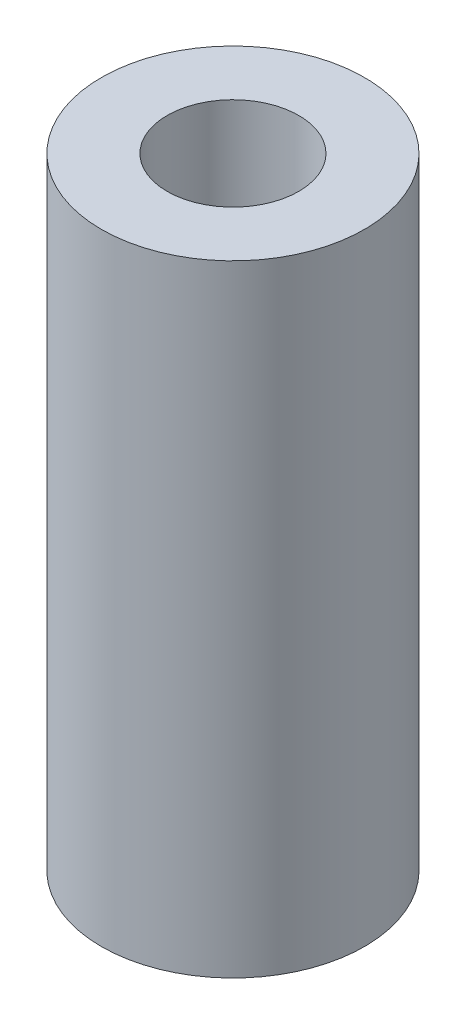
SolidWorks part; units mm, degrees
ref_plane "Front Plane" through (0, 0, 0) normal (0, 0, 1) x (1, 0, 0)
ref_plane "Top Plane" through (0, 0, 0) normal (0, 1, 0) x (1, 0, 0)
ref_plane "Right Plane" through (0, 0, 0) normal (1, 0, 0) x (0, 0, -1)
sketch "Sketch1" plane through (0, 0, 0) normal (0, 1, 0) x (1, 0, 0)
  circle A0 centre (0, 0) radius 15
  dimension "SLEEVE_OD" = 30
extrude "Boss-Extrude1" add sketch "Sketch1" along normal blind 70.81
sketch "Sketch2" plane through (0, 0, 0) normal (0, 1, 0) x (1, 0, 0)
  circle A0 centre (0, 0) radius 7.5034
  dimension "BORE_D" = 15.0069
extrude "Cut-Extrude1" cut sketch "Sketch2" along normal through all
chamfer "Chamfer1" distance 2.4833 angle 64.788 rebuild error yes
